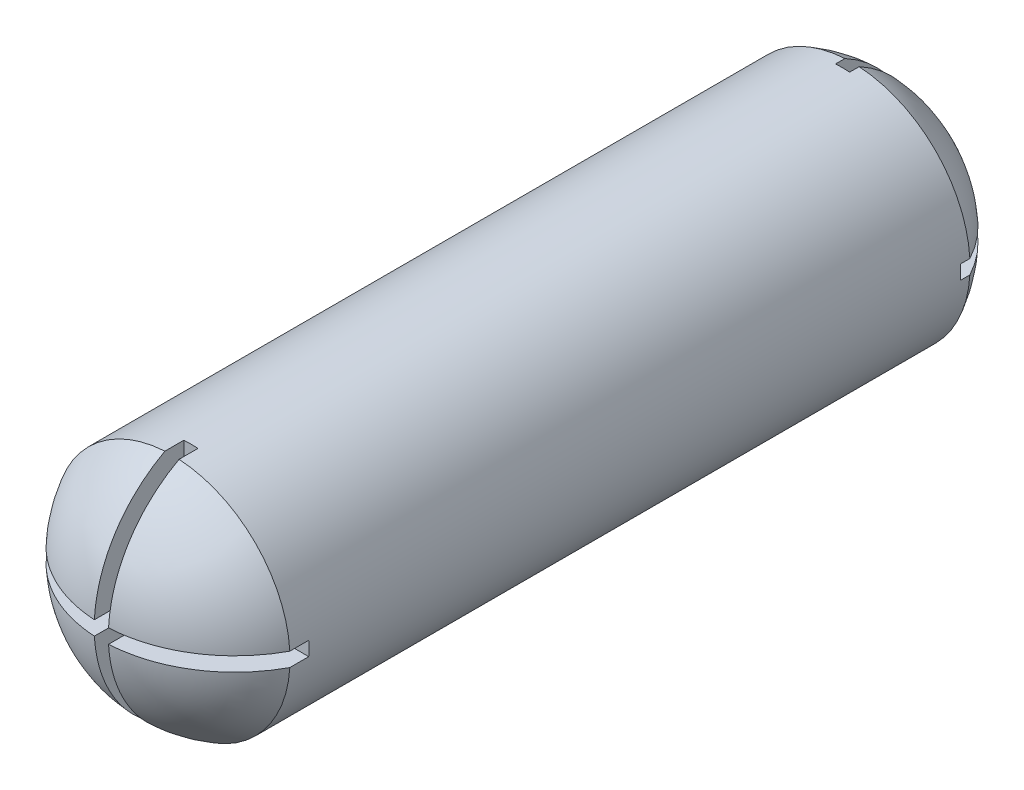
SolidWorks part; units mm, degrees
material "Chrome Stainless Steel"
ref_plane "Front Plane" through (0, 0, 0) normal (0, 0, 1) x (1, 0, 0)
ref_plane "Top Plane" through (0, 0, 0) normal (0, 1, 0) x (1, 0, 0)
ref_plane "Right Plane" through (0, 0, 0) normal (1, 0, 0) x (0, 0, -1)
sketch "Sketch1" plane through (0, 0, 0) normal (0, 0, 1) x (1, 0, 0)
  circle A0 centre (0, 0) radius 25
  dimension "D1" = 50
extrude "Boss-Extrude1" add sketch "Sketch1" along normal blind 144
dome "Dome1" faces to dome 1 distance 15 reverse direction no elliptical dome no face at (25, 0, 144) parameters "D1"=15
dome "Dome2" faces to dome 1 distance 15 reverse direction no elliptical dome no face at (25, 0, 0) parameters "D1"=15
sketch "Sketch2" plane through (0, 0, 0) normal (0, 0, 1) x (1, 0, 0)
  line L0 (-1.5, 1.5) -> (-24.955, 1.5)
  line L2 (1.5, -24.955) -> (1.5, -1.5)
  line L4 (-1.5, -24.955) -> (-1.5, -1.5)
  line L7 (24.955, 1.5) -> (1.5, 1.5)
  line L9 (24.955, -1.5) -> (1.5, -1.5)
  line L13 (1.5, 1.5) -> (1.5, 24.955)
  line L17 (-1.5, 1.5) -> (-1.5, 24.955)
  line L18 (-1.5, -1.5) -> (-24.955, -1.5)
  circle A0 centre (0, 0) radius 25 construction
  circle A1 centre (0, 0) radius 25
  point P1 (0, 0)
  point P7 (0, 0)
extrude "Cut-Extrude3" cut sketch "Sketch2" against normal blind 20 and the other way blind 2 contours L13 A1 L17 L0 L18 L4 L2 L9 L7 region at (0, 0, 0)
ref_plane "Plane1" through (0, 0, 170) normal (0, 0, 1) x (1, 0, 0)
sketch "Sketch3" plane through (0, 0, 170) normal (0, 0, 1) x (1, 0, 0)
  line L1 (-1.5, -27.2256) -> (1.5, -27.2256)
  line L2 (-1.5, -27.2256) -> (-1.5, 27.2256)
  line L3 (-1.5, 27.2256) -> (1.5, 27.2256)
  line L4 (1.5, -27.2256) -> (1.5, 27.2256)
  line L5 (-1.5, -27.2256) -> (1.5, 27.2256) construction
  line L6 (-1.5, 27.2256) -> (1.5, -27.2256) construction
  line L7 (-26.513, -1.5) -> (26.513, -1.5)
  line L8 (-26.513, -1.5) -> (-26.513, 1.5)
  line L9 (-26.513, 1.5) -> (26.513, 1.5)
  line L10 (26.513, -1.5) -> (26.513, 1.5)
  line L11 (-26.513, -1.5) -> (26.513, 1.5) construction
  line L12 (-26.513, 1.5) -> (26.513, -1.5) construction
  point P0 (0, 0)
  point P6 (0, 0)
  dimension "D1" = 3
  dimension "D2" = 3
extrude "Cut-Extrude4" cut sketch "Sketch3" against normal blind 30 contours L7 L2 L1 L4 | L2 L9 L4 L3 | L7 L10 L9 L4 | L9 L8 L7 L2 | L9 L2 L7 L4 region at (0, -14.3628, 170) region at (-14.0065, 0, 170) region at (0, 0, 170) region at (14.0065, 0, 170) region at (0, 14.3628, 170)
